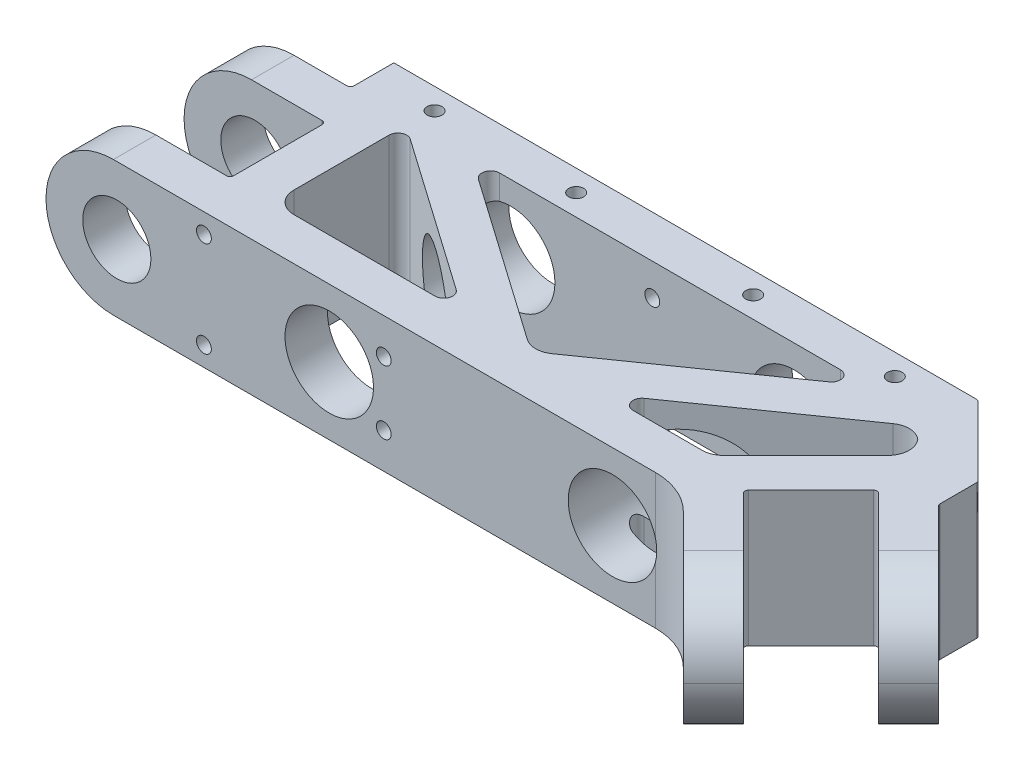
SolidWorks part; units mm, degrees
material "Delrin 150"
ref_plane "Front Plane" through (0, 0, 0) normal (0, 0, 1) x (1, 0, 0)
ref_plane "Top Plane" through (0, 0, 0) normal (0, 1, 0) x (1, 0, 0)
ref_plane "Right Plane" through (0, 0, 0) normal (1, 0, 0) x (0, 0, -1)
ref_axis "Axis1" through (0, 0, -88.99) along (0, 0, 1)
ref_axis "Axis2" through (0, -55, 0) along (0, 1, 0)
ref_axis "Axis3" through (-88.99, 0, 0) along (1, 0, 0)
sketch "Sketch1" plane through (0, 0, 0) normal (0, 1, 0) x (1, 0, 0)
  line L0 (-200, -91.5) -> (-200, -64.5) construction
  line L1 (-185, -40.25) -> (-185, -52.5)
  line L2 (-185, -52.5) -> (-220, -52.5)
  line L3 (-220, -52.5) -> (-220, -64.5)
  line L4 (-220, -64.5) -> (-180, -64.5)
  line L5 (-180, -64.5) -> (-180, -91.5)
  line L6 (-180, -91.5) -> (-220, -91.5)
  line L7 (-220, -91.5) -> (-220, -103.5)
  line L8 (-220, -103.5) -> (-39.9871, -103.5)
  line L9 (-39.9871, -103.5) -> (-11.3137, -132.1734)
  line L10 (-11.3137, -132.1734) -> (-2.8284, -123.6881)
  line L11 (-2.8284, -123.6881) -> (-31.1127, -95.4038)
  line L12 (-31.1127, -95.4038) -> (-12.0208, -76.3119)
  line L13 (-12.0208, -76.3119) -> (16.2635, -104.5962)
  line L14 (16.2635, -104.5962) -> (24.7487, -96.1109)
  line L15 (0, -71.3622) -> (0, -40.25)
  line L16 (0, -40.25) -> (-185, -40.25)
  line L17 (-16.9706, -109.5459) -> (2.1213, -90.4541) construction
  line L18 (-21.5668, -85.8579) -> (-67.1746, -40.25) construction
  line L19 (-200, -78) -> (-285.6315, -78) construction
  line L21 (0, 0) -> (-387.9586, 0) construction
  line L22 (0, 40.25) -> (0, -40.25) construction
  line L23 (-7.4246, -100) -> (-7.4246, 0) construction
  line L24 (24.7487, -96.1109) -> (0, -71.3622)
  dimension "D1" = 12
  dimension "D2" = 27
  dimension "D3" = 40
  dimension "D4" = 12
  dimension "D5" = 35
  dimension "D6" = 12
  dimension "D7" = 27
  dimension "D8" = 40
  dimension "D9" = 35
  dimension "D10" = 12
  dimension "D11" = 156
  dimension "D12" = 200
  dimension "D13" = 80.5
  dimension "D14" = 200
  dimension "D16" = 45
extrude "Boss-Extrude1" add sketch "Sketch1" along normal mid plane 38.1
sketch "Sketch2" plane through (0, 0, 103.5) normal (0, 0, 1) x (1, 0, 0)
  circle A0 centre (-200, 0) radius 9.625
  dimension "D1" = 19.25
extrude "Cut-Extrude1" cut sketch "Sketch2" against normal through all
sketch "Sketch3" plane through (-103.6227, 0, 39.8644) normal (0.7071, 0, -0.7071) x (-0.7071, 0, -0.7071)
  line L0 (-130.5446, 19.05) -> (-90.5446, -19.05) construction
  circle A0 centre (-110.5446, 0) radius 9.625
  dimension "D1" = 19.25
extrude "Cut-Extrude2" cut sketch "Sketch3" along normal through all
fillet "Fillet1" radius 19.05 8 edges at (-220, -19.05, 58.5) (-220, 19.05, 58.5) (-220, 19.05, 97.5) (-220, -19.05, 97.5) (20.5061, -19.05, 100.3536) (20.5061, 19.05, 100.3536) (-7.0711, 19.05, 127.9307) (-7.0711, -19.05, 127.9307)
fillet "Fillet3" radius 19.05 1 edges at (-39.9871, 0, 103.5)
chamfer "Chamfer1" distance 20 angle 45 1 edges at (0, 0, 40.25)
fillet "Fillet4" radius 1 8 edges at (-185, 0, 52.5) (-12.0208, 0, 76.3119) (-31.1127, 0, 95.4038) (-180, 0, 91.5) (-180, 0, 64.5) (0, 0, 71.3622) (-20, 0, 40.25) (0, 0, 60.25)
hole_wizard "Tap Drill for  Tap2" positions "Sketch14" profile "Sketch13" hole size "M5x0.8" standard "ANSI Metric"
sketch "Sketch14" plane through (0, 0, 40.25) normal (0, 0, -1) x (-1, 0, 0)
  line L0 (0, 0) -> (200, 0) construction
  line L3 (25, 10.05) -> (100, 10.05) construction
  line L4 (100, 10.05) -> (175, 10.05) construction
  line L6 (20.4142, 19.05) -> (185, 19.05) construction
  circle A0 centre (200, 0) radius 9.625 construction
  point P0 (25, 10.05)
  point P4 (100, 10.05)
  point P8 (175, 10.05)
  point P18 (175, -10.05)
  point P19 (100, -10.05)
  point P20 (25, -10.05)
  dimension "D1" = 25
  dimension "D2" = 75
  dimension "D3" = 9
sketch "Sketch13" plane through (-25, 10.05, 40.25) normal (1, 0, 0) x (0, 1, 0)
  line L0 (0, 0) -> (0, 16.2618)
  line L1 (0, 16.2618) -> (2.1, 15)
  line L2 (2.1, 15) -> (2.1, 0)
  line L5 (2.1, 0) -> (0, 0)
  line L10 (0, 16.2618) -> (-2.1, 15) construction
  line L11 (0, -6.35) -> (0, 107.95) construction
  dimension "Hole Dia." = 4.2
  dimension "Hole Depth" = 15
  dimension "Drill Angle" = 118
hole_wizard "Tap Drill for  Tap3" positions "Sketch18" profile "Sketch17" hole size "M5x0.8" standard "ANSI Metric"
sketch "Sketch18" plane through (0, 0, 103.5) normal (0, 0, 1) x (1, 0, 0)
  line L0 (-175.4, 0) -> (-150, 0) construction
  line L1 (-150, 0) -> (-150, 19.05) construction
  line L2 (-200.95, 19.05) -> (-47.8778, 19.05) construction
  line L4 (-150, 0) -> (-150, -19.05) construction
  line L5 (-200.95, -19.05) -> (-47.8778, -19.05) construction
  line L6 (-150, 0) -> (-124.6, 0) construction
  circle A0 centre (-200, 0) radius 9.625 construction
  point P0 (-175.4, 13.5)
  point P13 (-175.4, -13.5)
  point P14 (-124.6, -9)
  point P15 (-124.6, 9)
  dimension "D1" = 27
  dimension "D2" = 50.8
  dimension "D3" = 50
  dimension "D4" = 18
sketch "Sketch17" plane through (-175.4, 13.5, 103.5) normal (1, 0, 0) x (0, -1, 0)
  line L0 (0, 0) -> (0, 16.2618)
  line L1 (0, 16.2618) -> (2.1, 15)
  line L2 (2.1, 15) -> (2.1, 0)
  line L5 (2.1, 0) -> (0, 0)
  line L10 (0, 16.2618) -> (-2.1, 15) construction
  line L11 (0, -6.35) -> (0, 107.95) construction
  dimension "Hole Dia." = 4.2
  dimension "Hole Depth" = 15
  dimension "Drill Angle" = 118
sketch "Sketch19" plane through (0, -19.05, 0) normal (0, -1, 0) x (1, 0, 0)
  line L0 (-168, 91.5) -> (-168, 52.25)
  line L1 (-168, 52.25) -> (-24.9706, 52.25)
  line L2 (-24.9706, 52.25) -> (-14.95, 62.2706)
  line L3 (-14.95, 62.2706) -> (-44.1795, 91.5)
  line L4 (-44.1795, 91.5) -> (-168, 91.5)
  line L5 (-200.95, 103.5) -> (-47.8778, 103.5) construction
  line L6 (-180, 65.5) -> (-180, 90.5) construction
  line L7 (-20.4142, 40.25) -> (-185, 40.25) construction
  line L8 (-30.4056, 94.6967) -> (-12.7279, 77.019) construction
  line L9 (-19.7071, 40.5429) -> (-0.2929, 59.9571) construction
  line L10 (-38.9452, 52.25) -> (-95, 91.5)
  line L11 (-95, 91.5) -> (-151.0548, 52.25)
  line L12 (-18.0238, 52.25) -> (-74.0786, 91.5)
  line L13 (-59.8666, 52.25) -> (-95.8717, 77.4611)
  line L14 (-95.8717, 77.4611) -> (-131.8769, 52.25)
  line L15 (-114.1779, 91.5) -> (-170.2327, 52.25)
  line L16 (-95, 91.5) -> (-95, 52.25) construction
  dimension "D1" = 12
  dimension "D2" = 12
  dimension "D3" = 12
  dimension "D4" = 12
  dimension "D5" = 12
  dimension "D6" = 12
  dimension "D7" = 11
  dimension "D8" = 85
  dimension "D9" = 110
extrude "Cut-Extrude10" cut sketch "Sketch19" against normal through all contours L15 L4 L0 L1 | L16 L11 L1 L14 | L16 L14 L1 | L13 L16 L1 | L10 L16 L13 L1 | L12 L1 L2 L3 L4 region at (-150.0593, -19.05, 78.9378) region at (-118.5429, -19.05, 68.7562) region at (-71.8029, -19.05, 68.4928) region at (-41.3136, -19.05, 76.6635) region at (-107.3057, -19.05, 60.8386) region at (-83.2889, -19.05, 60.4502)
fillet "Fillet8" [suppressed] radius 6
fillet "Fillet9" radius 2.5 2 edges at (-38.9452, 0, 52.25) (-151.0548, 0, 52.25)
fillet "Fillet11" radius 6 5 edges at (-168, 0, 91.5) (-95, 0, 91.5) (-22.1096, 0, 55.1109) (-44.1795, 0, 91.5) (-14.95, 0, 62.2706)
fillet "Fillet12" radius 2.5 3 edges at (-114.1779, 0, 91.5) (-74.0786, 0, 91.5) (-168, 0, 53.8134)
hole_wizard "Tap Drill for M5x0.8 Tap1" positions "Sketch21" profile "Sketch20" hole size "M5x0.8" standard "ANSI Metric" end condition through all
sketch "Sketch21" plane through (0, 19.05, 0) normal (0, 1, 0) x (1, 0, 0)
  line L0 (-102.5, -40.25) -> (-102.5, -52.25) construction
  line L1 (-20.4142, -40.25) -> (-185, -40.25) construction
  line L2 (-143.1258, -52.25) -> (-46.8742, -52.25) construction
  line L4 (-102.5, -46.25) -> (-127.5, -46.25) construction
  line L6 (-185, -40.25) -> (-185, -51.5) construction
  point P0 (-37.5, -46.25)
  point P2 (-77.5, -46.25)
  point P4 (-127.5, -46.25)
  point P6 (-167.5, -46.25)
  dimension "D1" = 17.5
  dimension "D2" = 130
  dimension "D3" = 50
sketch "Sketch20" plane through (-37.5, 19.05, 46.25) normal (1, 0, 0) x (0, 0, 1)
  line L0 (0, 0) -> (0, 38.1)
  line L1 (0, 38.1) -> (2.1, 38.1)
  line L2 (2.1, 38.1) -> (2.1, 0)
  line L5 (2.1, 0) -> (0, 0)
  line L11 (0, -6.35) -> (0, 107.95) construction
  dimension "Thru Hole Dia." = 4.2
  dimension "Thru Hole Depth" = 38.1
sketch "Sketch4" plane through (0, 0, 40.25) normal (0, 0, -1) x (-1, 0, 0)
  line L0 (25, -10.05) -> (100, 10.05) construction
  line L1 (100, 10.05) -> (175, -10.05) construction
  line L2 (62.5, 0) -> (137.5, 0) construction
  line L3 (100, 10.05) -> (100, 0) construction
  circle A0 centre (80, 0) radius 7.5
  circle A1 centre (120, 0) radius 7.5
  dimension "D1" = 15
  dimension "D2" = 40
extrude "Boss-Extrude2" [suppressed] add sketch "Sketch4" along normal blind 3.5
sketch "Sketch23" plane through (0, 0, 40.25) normal (0, 0, 1) x (1, 0, 0)
  line L0 (-140, 0) -> (-60, 0) construction
  line L1 (-100, 10.05) -> (-100, 0) construction
  line L3 (-100, 0) -> (-100, -10.05) construction
  circle A0 centre (-140, 0) radius 12.5
  circle A1 centre (-60, 0) radius 12.5
  dimension "D1" = 25
  dimension "D2" = 80
extrude "Cut-Extrude11" cut sketch "Sketch23" along normal through all
